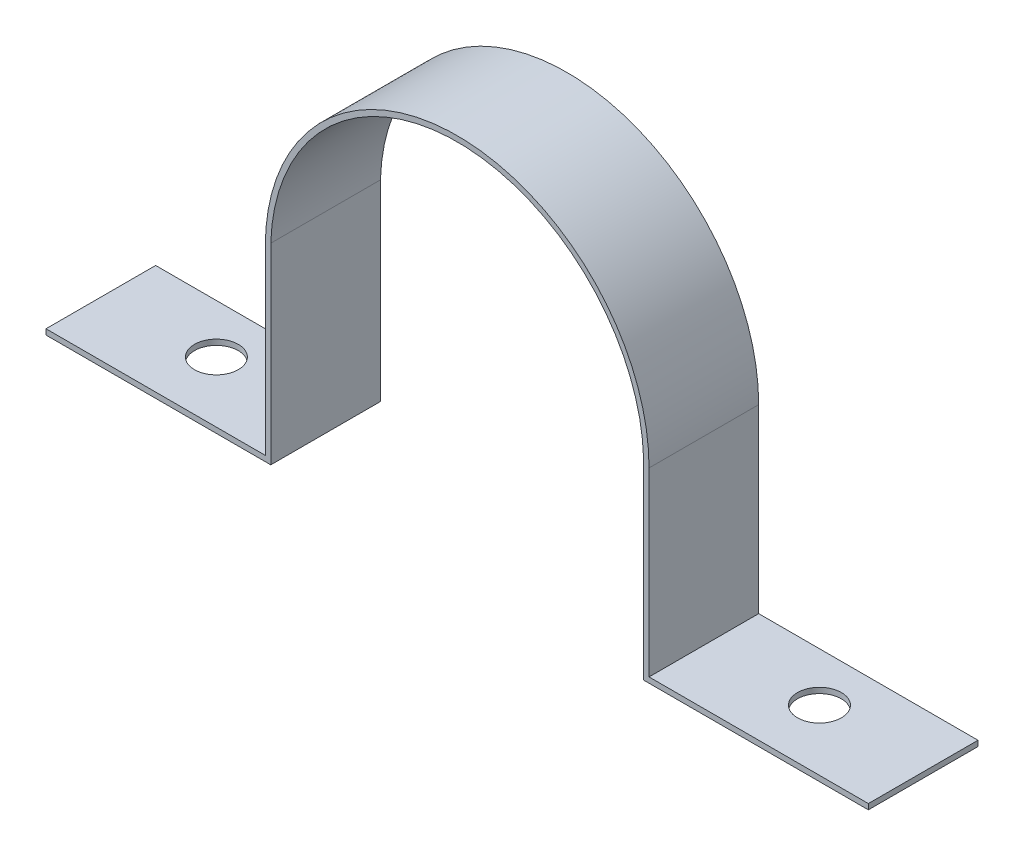
SolidWorks part; units mm, degrees
ref_plane "Alzado" through (0, 0, 0) normal (0, 0, 1) x (1, 0, 0)
ref_plane "Planta" through (0, 0, 0) normal (0, 1, 0) x (1, 0, 0)
ref_plane "Vista lateral" through (0, 0, 0) normal (1, 0, 0) x (0, 0, -1)
sketch "Croquis1" plane through (0, 0, 0) normal (0, 0, 1) x (1, 0, 0)
  line L7 (0, 0) -> (0, -10.2182) construction
  line L12 (-17.5, 0) -> (-17.5, -16.5074)
  line L14 (17, 0.5) -> (17, -17.0074)
  line L16 (-17, 0.5) -> (-17, -17.0074)
  line L17 (17, 17.0074) -> (-17, -17.0074) construction
  line L18 (17, -17.0074) -> (-17, 17.0074) construction
  line L20 (17.5, 0) -> (17.5, -16.5074)
  line L22 (-17, -17.0074) -> (-37.5, -17.0074)
  line L23 (-37.5, -17.0074) -> (-37.5, -16.5074)
  line L24 (-37.5, -16.5074) -> (-17.5, -16.5074)
  line L25 (-17.5, 17.5074) -> (-17.5, -17.5074) construction
  line L26 (17.5, -17.5074) -> (-17.5, -17.5074) construction
  line L27 (37.5, -16.5074) -> (17.5, -16.5074)
  line L28 (37.5, -17.0074) -> (37.5, -16.5074)
  line L29 (17, -17.0074) -> (37.5, -17.0074)
  line L30 (17.5, 17.5074) -> (17.5, -17.5074) construction
  line L31 (17, -17.0074) -> (-17, -17.0074) construction
  line L32 (17.5, 17.5074) -> (-17.5, 17.5074) construction
  line L33 (17, 17.0074) -> (-17, 17.0074) construction
  line L34 (-17, 17.0074) -> (-17, -17.0074) construction
  line L35 (17, 17.0074) -> (17, -17.0074) construction
  arc A1 (17.5, 0) -> (-17.5, 0) centre (0, 0) ccw
  arc A4 (17, 0.5) -> (-17, 0.5) centre (0, 0) ccw
  dimension "D1" = 17.5
  dimension "D2" = 0.5
  dimension "D6" = 17.0074
  dimension "D3" = 20
  dimension "D5" = 17.5074
extrude "Saliente-Extruir1" add sketch "Croquis1" along normal blind 10
sketch "Croquis2" plane through (0, -16.5074, 0) normal (0, 1, 0) x (1, 0, 0)
  line L0 (-17.5, -10) -> (-17.5, 0) construction
  line L1 (17.5, -10) -> (17.5, 0) construction
  circle A0 centre (-27.5, -4.4614) radius 2
  circle A1 centre (27.5, -4.4614) radius 2
  dimension "D1" = 10
  dimension "D2" = 10
extrude "Cortar-Extruir1" cut sketch "Croquis2" against normal blind 10
